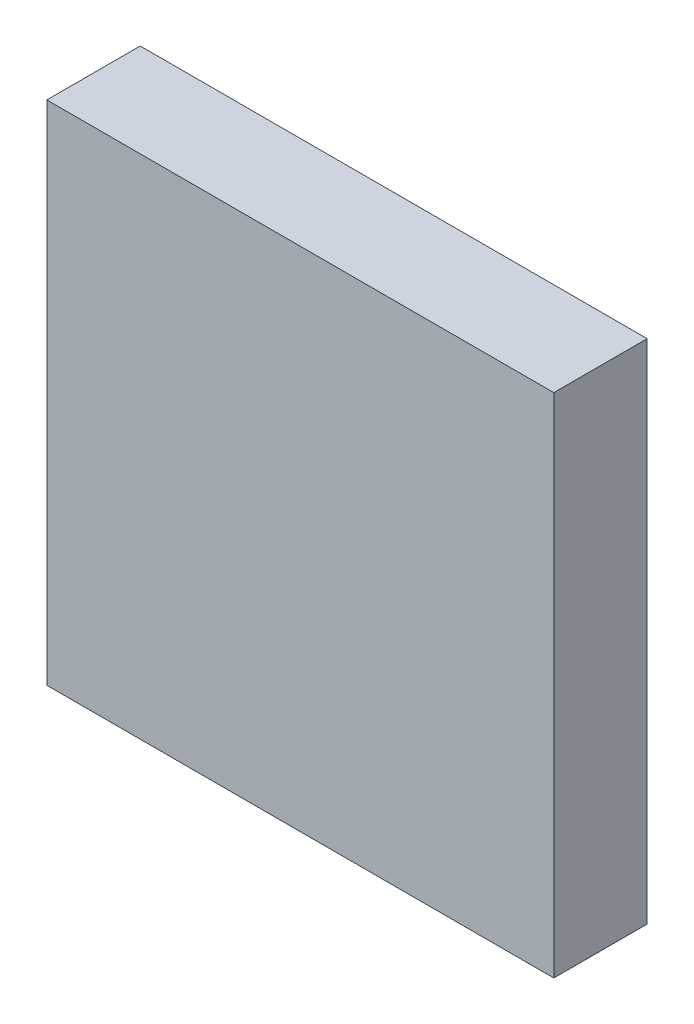
SolidWorks part; units mm, degrees
ref_plane "Front Plane" through (0, 0, 0) normal (0, 0, 1) x (1, 0, 0)
ref_plane "Top Plane" through (0, 0, 0) normal (0, 1, 0) x (1, 0, 0)
ref_plane "Right Plane" through (0, 0, 0) normal (1, 0, 0) x (0, 0, -1)
sketch "Sketch1" plane through (0, 0, 0) normal (0, 0, 1) x (1, 0, 0)
  line L1 (-19, 19) -> (19, 19)
  line L2 (-19, 19) -> (-19, -19)
  line L3 (-19, -19) -> (19, -19)
  line L4 (19, 19) -> (19, -19)
  line L5 (-19, 19) -> (19, -19) construction
  line L6 (-19, -19) -> (19, 19) construction
  point P0 (0, 0)
extrude "Boss-Extrude1" add sketch "Sketch1" along normal blind 7
